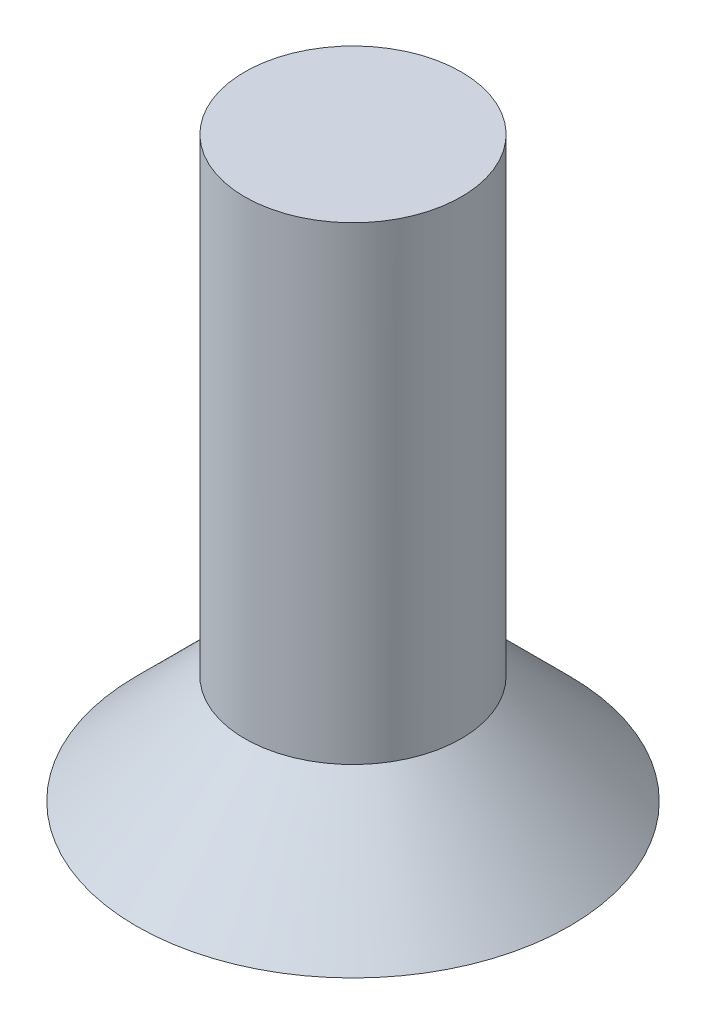
SolidWorks part; units mm, degrees
material "Plain Carbon Steel"
ref_plane "Front Plane" through (0, 0, 0) normal (0, 0, 1) x (1, 0, 0)
ref_plane "Top Plane" through (0, 0, 0) normal (0, 1, 0) x (1, 0, 0)
ref_plane "Right Plane" through (0, 0, 0) normal (1, 0, 0) x (0, 0, -1)
sketch "Sketch1" plane through (0, 0, 0) normal (0, 1, 0) x (1, 0, 0)
  circle A0 centre (0, 0) radius 3
  dimension "D1" = 6
extrude "Boss-Extrude1" add sketch "Sketch1" along normal blind 2.5
sketch "Sketch2" plane through (0, 2.5, 0) normal (0, 1, 0) x (1, 0, 0)
  circle A0 centre (0, 0) radius 1.5
  dimension "D1" = 3
extrude "Boss-Extrude2" add sketch "Sketch2" along normal blind 5.5
chamfer "Chamfer1" distance 2.5 angle 45 1 edges at (0, 2.5, 3)
sketch "Sketch3" plane through (0, 0, 0) normal (0, -1, 0) x (1, 0, 0)
  line L1 (1.2512, -0.897) -> (1.4024, 0.6351)
  line L2 (1.4024, 0.6351) -> (0.1512, 1.532)
  line L3 (0.1512, 1.532) -> (-1.2512, 0.897)
  line L4 (-1.2512, 0.897) -> (-1.4024, -0.6351)
  line L5 (-1.4024, -0.6351) -> (-0.1512, -1.532)
  line L6 (-0.1512, -1.532) -> (1.2512, -0.897)
  circle A0 centre (0, 0) radius 1.3332 construction
extrude "Cut-Extrude1" cut sketch "Sketch3" against normal blind 1
